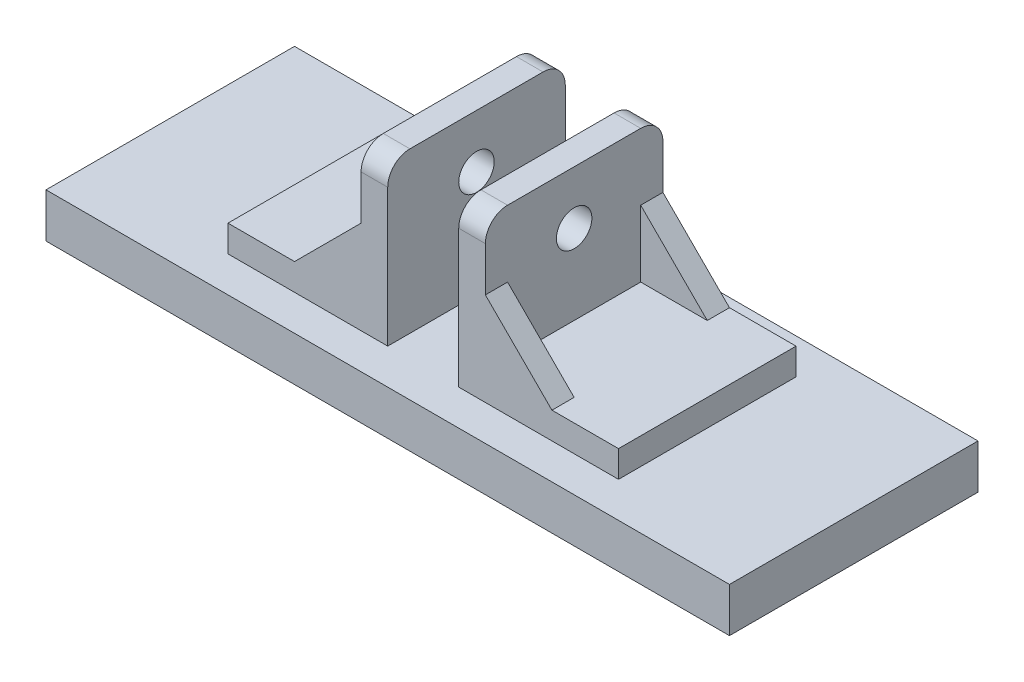
SolidWorks part; units mm, degrees
ref_plane "Front Plane" through (0, 0, 0) normal (0, 0, 1) x (1, 0, 0)
ref_plane "Top Plane" through (0, 0, 0) normal (0, 1, 0) x (1, 0, 0)
ref_plane "Right Plane" through (0, 0, 0) normal (1, 0, 0) x (0, 0, -1)
sketch "Sketch1" plane through (0, 0, 0) normal (0, 1, 0) x (1, 0, 0)
  line L1 (77, 28) -> (-77, 28)
  line L2 (77, 28) -> (77, -28)
  line L3 (77, -28) -> (-77, -28)
  line L4 (-77, 28) -> (-77, -28)
  line L5 (77, 28) -> (-77, -28) construction
  line L6 (77, -28) -> (-77, 28) construction
  point P0 (0, 0)
  dimension "D1" = 154
  dimension "D2" = 56
extrude "plate" add sketch "Sketch1" along normal blind 10
sketch "Sketch2" plane through (0, 0, 0) normal (0, 0, 1) x (1, 0, 0)
  line L0 (-8, 10) -> (-8, 46)
  line L1 (-77, 10) -> (77, 10) construction
  line L2 (-8, 46) -> (-14, 46)
  line L3 (-14, 46) -> (-14, 16)
  line L4 (-14, 16) -> (-44, 16)
  line L5 (-44, 16) -> (-44, 10)
  line L6 (-44, 10) -> (-8, 10)
  line L7 (-14, 31) -> (-29, 16)
  line L8 (0, 0) -> (0, 10) construction
  line L9 (14, 31) -> (29, 16)
  line L10 (44, 16) -> (44, 10)
  line L11 (14, 16) -> (44, 16)
  line L12 (14, 46) -> (14, 16)
  line L13 (8, 46) -> (14, 46)
  line L14 (8, 10) -> (8, 46)
  line L15 (44, 10) -> (8, 10)
  dimension "D1" = 45
  dimension "D2" = 6
  dimension "D3" = 8
  dimension "D4" = 36
  dimension "D5" = 15
extrude "Boss-Extrude1" add sketch "Sketch2" along normal mid plane 40 contours L0 L2 L3 L4 L5 L6 | L10 L15 L14 L13 L12 L11
extrude "Corner" add sketch "Sketch2<4>" against normal blind 5 from offset 15 contours L3 L7 L4 | L9 L12 L11 region at (-19, 21, 0) region at (19, 21, 0) offset against normal yes
sketch "Sketch2<4>" plane through (0, 0, 0) normal (0, 0, 1) x (1, 0, 0) same geometry as "Sketch2"
extrude "Corner2" add sketch "Sketch2<3>" along normal blind 5 from offset 15 contours L3 L7 L4 | L9 L12 L11 region at (-19, 21, 0) region at (19, 21, 0)
sketch "Sketch2<3>" plane through (0, 0, 0) normal (0, 0, 1) x (1, 0, 0) same geometry as "Sketch2"
sketch "Sketch3" plane through (-14, 0, 0) normal (-1, 0, 0) x (0, 0, 1)
  line L0 (20, 46) -> (-20, 46) construction
  circle A0 centre (0, 34) radius 4
  dimension "D2" = 8
  dimension "D1" = 12
extrude "Cut-Extrude1" cut sketch "Sketch3" against normal up to surface (28 mm away) up to face at (14, 31, 0)
fillet "Fillet1" radius 5 4 edges at (-11, 46, -20) (11, 46, 20) (11, 46, -20) (-11, 46, 20)
equation "\"D1@Sketch1\"=144 + 10"
equation "\"D2@Sketch1\"=46+10"
